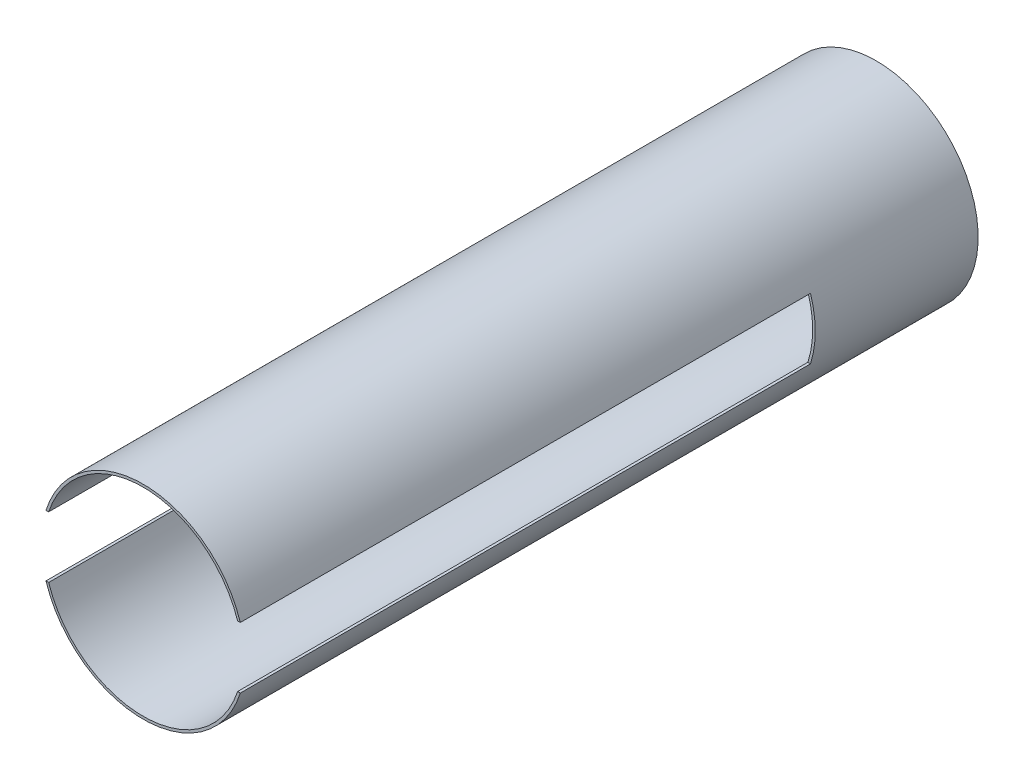
SolidWorks part; units mm, degrees
ref_plane "Front Plane" through (0, 0, 0) normal (0, 0, 1) x (1, 0, 0)
ref_plane "Top Plane" through (0, 0, 0) normal (0, 1, 0) x (1, 0, 0)
ref_plane "Right Plane" through (0, 0, 0) normal (1, 0, 0) x (0, 0, -1)
sketch "Sketch1" plane through (0, 0, 0) normal (0, 0, 1) x (1, 0, 0)
  line L1 (-88.9, -19.05) -> (88.9, -19.05)
  line L2 (-88.9, -19.05) -> (-88.9, 19.05) construction
  line L3 (-88.9, 19.05) -> (88.9, 19.05)
  line L4 (88.9, -19.05) -> (88.9, 19.05) construction
  line L5 (-88.9, -19.05) -> (88.9, 19.05) construction
  line L6 (-88.9, 19.05) -> (88.9, -19.05) construction
  circle A0 centre (0, 0) radius 63.5
  circle A1 centre (0, 0) radius 61.9125
  dimension "D1" = 127
  dimension "D4" = 1.5875
  dimension "D2" = 38.1
  dimension "D3" = 177.8
extrude "Boss-Extrude1" add sketch "Sketch1" along normal mid plane 355.6 contours A1 L3 A0 | A1 L1 A0 region at (-59.742, -20.3405, 0) region at (0, 62.2095, 0)
sketch "Sketch2" plane through (0, 0, -177.8) normal (0, 0, -1) x (-1, 0, 0)
  circle A0 centre (0, 0) radius 63.5 construction
  circle A1 centre (0, 0) radius 61.9125 construction
  circle A2 centre (0, 0) radius 63.5
  circle A3 centre (0, 0) radius 61.9125
extrude "Boss-Extrude2" add sketch "Sketch2" along normal blind 101.6
